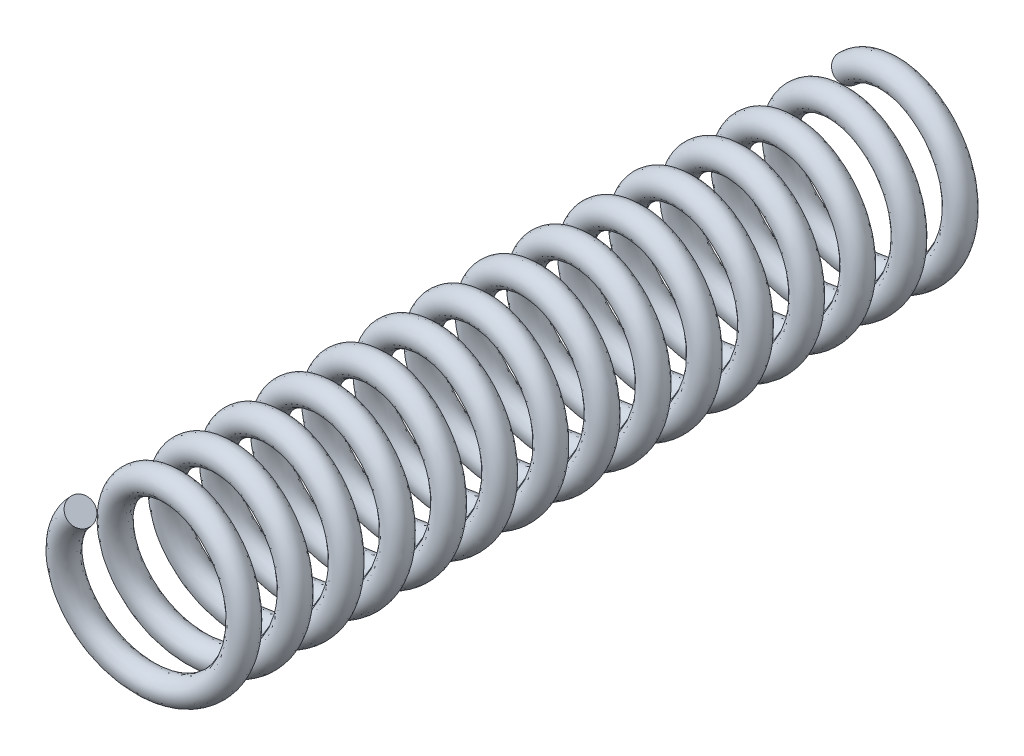
SolidWorks part; units mm, degrees
ref_plane "前视基准面" through (0, 0, 0) normal (0, 0, 1) x (1, 0, 0)
ref_plane "上视基准面" through (0, 0, 0) normal (0, 1, 0) x (1, 0, 0)
ref_plane "右视基准面" through (0, 0, 0) normal (1, 0, 0) x (0, 0, -1)
sketch "草图1" plane through (0, 0, 0) normal (0, 0, 1) x (1, 0, 0)
  circle A0 centre (0, 0) radius 1.5
  dimension "D1" = 3
curve "螺旋线/涡状线1" pitch 1 height 15 turns 15
sweep "扫描1" add path "螺旋线/涡状线1" circular profile diameter 0.5 parameters "D3"=0.5
sketch "草图10" plane through (0, 0, 0) normal (0, 0, 1) x (1, 0, 0)
  circle A0 centre (0, 0) radius 2.4908 construction
